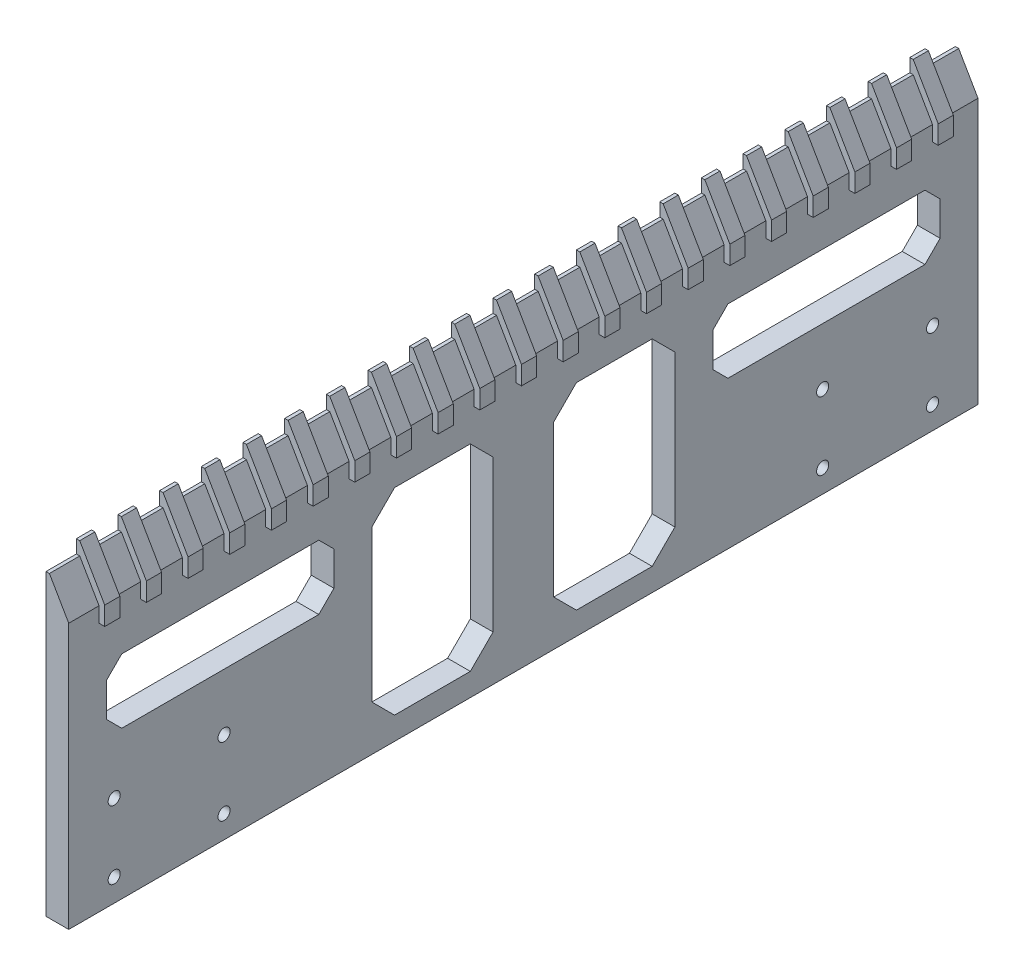
SolidWorks part; units mm, degrees
ref_plane "前视基准面" through (0, 0, 0) normal (0, 0, 1) x (1, 0, 0)
ref_plane "上视基准面" through (0, 0, 0) normal (0, 1, 0) x (1, 0, 0)
ref_plane "右视基准面" through (0, 0, 0) normal (1, 0, 0) x (0, 0, -1)
sketch "草图1" plane through (0, 0, 0) normal (1, 0, 0) x (0, 0, -1)
  line L1 (0, 0) -> (240, 0)
  line L2 (0, 0) -> (0, -70)
  line L3 (0, -70) -> (240, -70)
  line L4 (240, 0) -> (240, -70)
  dimension "D1" = 240
  dimension "D2" = 70
extrude "凸台-拉伸1" add sketch "草图1" along normal blind 6
sketch "草图3" plane through (6, 0, 0) normal (1, 0, 0) x (0, 0, -1)
  line L0 (120, 0) -> (120, -70) construction
  line L1 (14, -14) -> (66, -14)
  line L2 (10, -18) -> (10, -27)
  line L3 (14, -31) -> (66, -31)
  line L4 (70, -18) -> (70, -27)
  line L5 (240, 0) -> (0, 0) construction
  line L6 (0, -70) -> (240, -70) construction
  line L7 (0, 0) -> (0, -70) construction
  line L12 (10, -18) -> (14, -14)
  line L13 (10, -27) -> (14, -31)
  line L14 (66, -31) -> (70, -27)
  line L15 (66, -14) -> (70, -18)
  line L28 (80, -18) -> (86, -12)
  line L42 (86, -12) -> (106, -12)
  line L43 (80, -18) -> (80, -58)
  line L44 (86, -64) -> (106, -64)
  line L45 (112, -18) -> (112, -58)
  line L46 (106, -12) -> (112, -18)
  line L47 (106, -64) -> (112, -58)
  line L48 (80, -58) -> (86, -64)
  point P0 (10, -14)
  point P1 (70, -31)
  point P2 (10, -31)
  point P3 (70, -14)
  point P20 (80, -12)
  point P21 (112, -64)
  point P22 (80, -64)
  point P23 (112, -12)
  dimension "D1" = 10
  dimension "D2" = 14
  dimension "D3" = 17
  dimension "D4" = 60
  dimension "D5" = 12
  dimension "D6" = 6
  dimension "D7" = 52
  dimension "D12" = 80
  dimension "D13" = 8
  dimension "D14" = 32
extrude "切除-拉伸2" cut sketch "草图3" against normal through all
sketch "草图2" plane through (0, 0, 0) normal (1, 0, 0) x (0, 0, -1)
  line L0 (0, 0) -> (0, -70) construction
  line L1 (12, -46) -> (41, -46) construction
  line L2 (12, -46) -> (12, -64) construction
  line L3 (12, -64) -> (41, -64) construction
  line L4 (41, -46) -> (41, -64) construction
  line L5 (240, 0) -> (0, 0) construction
  line L6 (120, 0) -> (120, -70) construction
  circle A0 centre (12, -46) radius 1.55
  circle A1 centre (41, -64) radius 1.55
  circle A2 centre (41, -46) radius 1.55
  circle A3 centre (12, -64) radius 1.55
  dimension "D5" = 3.1
  dimension "D1" = 12
  dimension "D2" = 46
  dimension "D3" = 29
  dimension "D4" = 18
sketch "草图6" plane through (0, 0, 0) normal (0, 0, 1) x (1, 0, 0)
  line L0 (6, 0) -> (0, 0)
  line L1 (0, 0) -> (0, 8.8335)
  line L2 (0.9, 8.8335) -> (6, 0)
  line L3 (0, 8.8335) -> (0.9, 8.8335)
  line L4 (0, 8.8335) -> (0, 10.3923) construction
  line L5 (0, 10.3923) -> (0.9, 8.8335) construction
  dimension "D1" = 30
  dimension "D2" = 0.9
extrude "凸台-拉伸2" add sketch "草图6" against normal blind 240
ref_plane "基准面1" through (0, 0, -120) normal (0, 0, 1) x (1, 0, 0)
sketch "草图8" plane through (0, 0, -120) normal (0, 0, 1) x (1, 0, 0)
  line L0 (0, 10.3923) -> (0, 12.3335)
  line L1 (0.9, 12.3335) -> (7.5, 0.9019)
  line L2 (7.5, 0.9019) -> (7.5, -4)
  line L3 (7.5, -4) -> (6, -4)
  line L4 (6, 0) -> (6, -70) construction
  line L5 (6, -4) -> (6, 0)
  line L6 (6, 0) -> (0.9, 8.8335) construction
  line L7 (6, 0) -> (0.9, 8.8335)
  line L8 (0, 12.3335) -> (0.9, 12.3335)
  line L9 (0, 12.3335) -> (0, 13.8923) construction
  line L10 (0, 13.8923) -> (0.9, 12.3335) construction
  line L11 (0, 10.3923) -> (0, 8.8335)
  line L12 (0, 8.8335) -> (0.9, 8.8335)
  line L13 (0.9, 8.8335) -> (0, 10.3923) construction
  dimension "D1" = 3.5
  dimension "D2" = 1.5
  dimension "D3" = 4
  dimension "D4" = 0.9
extrude "凸台-拉伸3" add sketch "草图8" along normal mid plane 4
pattern_linear "阵列(线性)1" count 11 spacing 11 along (0, 0, 1) count 11 spacing 11 along (0, 0, -1) of "凸台-拉伸3"
hole_wizard "打孔尺寸(%根据)内六角圆柱头螺钉的类型1" positions "草图14" profile "草图15" counterbore size "M3" standard "GB" end condition through all
sketch "草图14" plane through (0, 0, 0) normal (-1, 0, 0) x (0, 0, 1)
  point P0 (-41, -46)
  point P3 (-12, -46)
  point P6 (-12, -64)
  point P9 (-41, -64)
sketch "草图15" plane through (0, -46, -41) normal (0, 1, 0) x (0, 0, 1)
  line L0 (0, 0) -> (0, 7.5)
  line L1 (0, 7.5) -> (1.6, 7.5)
  line L3 (1.6, 7.5) -> (1.6, 3.4)
  line L4 (1.6, 3.4) -> (3, 3.4)
  line L5 (3, 3.4) -> (3, 0)
  line L7 (3, 0) -> (0, 0)
  line L11 (0, -6.35) -> (0, 107.95) construction
  dimension "通孔孔直径" = 3.2
  dimension "通孔孔深度" = 7.5
  dimension "柱形沉头孔直径" = 6
  dimension "柱形沉头孔深度" = 3.4
mirror "镜向1" about plane through (0, 0, -120) normal (0, 0, 1) of "打孔尺寸(%根据)内六角圆柱头螺钉的类型1"
mirror "镜向2" about plane through (0, 0, -120) normal (0, 0, 1) of "切除-拉伸2"
